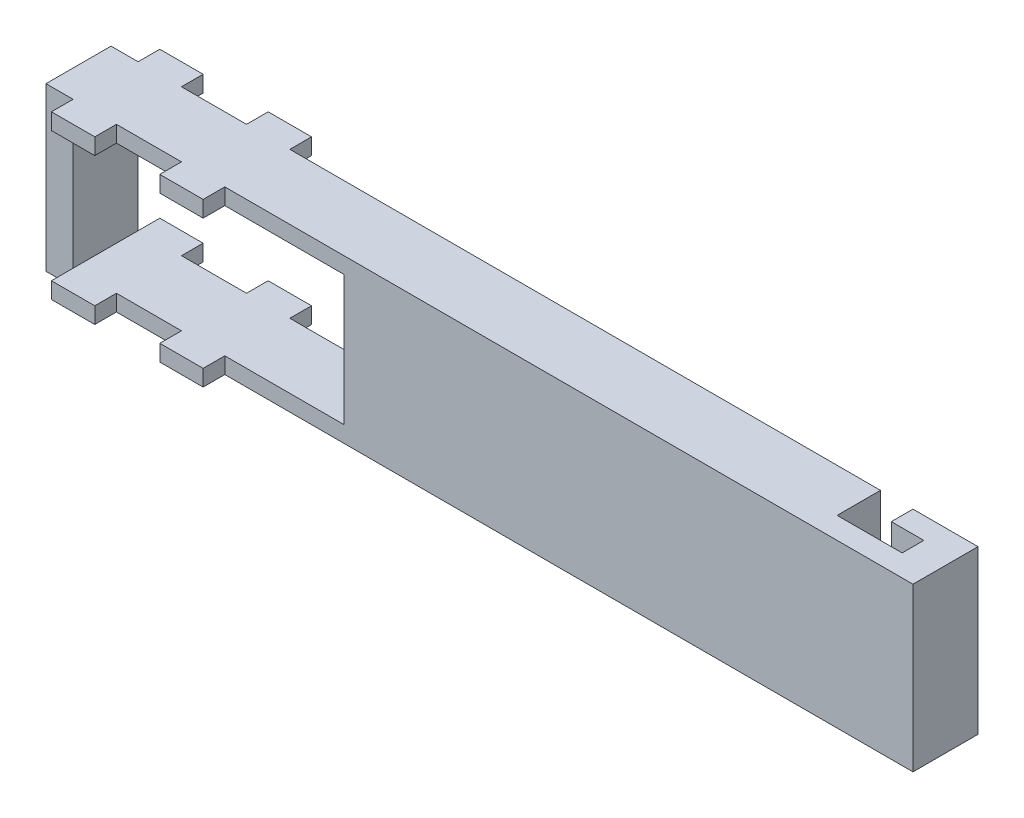
SolidWorks part; units mm, degrees
ref_plane "Front Plane" through (0, 0, 0) normal (0, 0, 1) x (1, 0, 0)
ref_plane "Top Plane" through (0, 0, 0) normal (0, 1, 0) x (1, 0, 0)
ref_plane "Right Plane" through (0, 0, 0) normal (1, 0, 0) x (0, 0, -1)
sketch "Sketch1" plane through (0, 0, 0) normal (0, 0, 1) x (1, 0, 0)
  line L1 (0, 0) -> (80, 0)
  line L2 (0, 0) -> (0, 15)
  line L3 (0, 15) -> (80, 15)
  line L4 (80, 0) -> (80, 15)
  dimension "D1" = 80
  dimension "D2" = 15
extrude "Boss-Extrude1" add sketch "Sketch1" along normal blind 6 contours L3 L4 L1 L2
sketch "Sketch2" plane through (0, 15, 0) normal (0, 1, 0) x (1, 0, 0)
  line L0 (74, 0) -> (74, -2)
  line L1 (0, 0) -> (80, 0) construction
  line L2 (74, -2) -> (77, -2)
  line L3 (77, -2) -> (77, -4)
  line L4 (77, -4) -> (71, -4)
  line L5 (71, -4) -> (71, 0)
  line L6 (71, 0) -> (74, 0)
  line L7 (80, -6) -> (80, 0) construction
  dimension "D1" = 9
  dimension "D2" = 2
  dimension "D3" = 2
  dimension "D4" = 6
  dimension "D5" = 3
extrude "Cut-Extrude1" cut sketch "Sketch2" against normal through all
sketch "Sketch3" plane through (0, 0, 6) normal (0, 0, 1) x (1, 0, 0)
  line L0 (0, 0) -> (0, 15) construction
  line L1 (2.5, 13.5) -> (27.5, 13.5)
  line L2 (2.5, 13.5) -> (2.5, 1.5)
  line L3 (2.5, 1.5) -> (27.5, 1.5)
  line L4 (27.5, 13.5) -> (27.5, 1.5)
  line L5 (0, 15) -> (80, 15) construction
  dimension "D1" = 12
  dimension "D2" = 2.5
  dimension "D3" = 1.5
  dimension "D4" = 25
extrude "Cut-Extrude2" cut sketch "Sketch3" against normal through all
sketch "Sketch4" plane through (0, 0, 6) normal (0, 0, 1) x (1, 0, 0)
  line L0 (0, 15) -> (80, 15) construction
  line L1 (2.5, 13.5) -> (6.5, 13.5)
  line L2 (2.5, 13.5) -> (2.5, 15)
  line L3 (2.5, 15) -> (6.5, 15)
  line L4 (6.5, 13.5) -> (6.5, 15)
  dimension "D1" = 4
extrude "Boss-Extrude2" add sketch "Sketch4" along normal blind 2
sketch "Sketch5" plane through (0, 0, 6) normal (0, 0, 1) x (1, 0, 0)
  line L0 (27.5, 13.5) -> (6.5, 13.5) construction
  line L1 (12.5, 13.5) -> (16.5, 13.5)
  line L2 (12.5, 13.5) -> (12.5, 15)
  line L3 (12.5, 15) -> (16.5, 15)
  line L4 (16.5, 13.5) -> (16.5, 15)
  line L5 (6.5, 15) -> (80, 15) construction
  line L6 (6.5, 13.5) -> (6.5, 15) construction
  dimension "D1" = 4
  dimension "D2" = 6
extrude "Boss-Extrude3" add sketch "Sketch5" along normal blind 2
sketch "Sketch6" plane through (0, 0, 6) normal (0, 0, 1) x (1, 0, 0)
  line L0 (0, 0) -> (80, 0) construction
  line L1 (2.5, 1.5) -> (6.5, 1.5)
  line L2 (2.5, 1.5) -> (2.5, 0)
  line L3 (2.5, 0) -> (6.5, 0)
  line L4 (6.5, 1.5) -> (6.5, 0)
  dimension "D1" = 4
sketch "Sketch7" plane through (0, 0, 6) normal (0, 0, 1) x (1, 0, 0)
  line L0 (2.5, 1.5) -> (27.5, 1.5) construction
  line L1 (12.5, 1.5) -> (16.5, 1.5)
  line L2 (12.5, 1.5) -> (12.5, 0)
  line L3 (12.5, 0) -> (16.5, 0)
  line L4 (16.5, 1.5) -> (16.5, 0)
  line L5 (0, 0) -> (80, 0) construction
  line L6 (12.5, 15) -> (12.5, 13.5) construction
  dimension "D1" = 0
  dimension "D2" = 4
extrude "Boss-Extrude4" add sketch "Sketch6" along normal blind 2 contours L4 L3 L2 L1
extrude "Boss-Extrude5" add sketch "Sketch7" along normal blind 2 contours L4 L3 L2 L1
sketch "Sketch9" plane through (0, 0, 0) normal (0, 0, -1) x (-1, 0, 0)
  line L0 (0, 15) -> (-71, 15) construction
  line L1 (-2.5, 13.5) -> (-6.5, 13.5)
  line L2 (-2.5, 13.5) -> (-2.5, 15)
  line L3 (-2.5, 15) -> (-6.5, 15)
  line L4 (-6.5, 13.5) -> (-6.5, 15)
  line L5 (-2.5, 13.5) -> (-2.5, 1.5) construction
  line L6 (-27.5, 13.5) -> (-2.5, 13.5) construction
  dimension "D1" = 4
  dimension "D2" = 0
  dimension "D3" = 0
extrude "Boss-Extrude6" add sketch "Sketch9" along normal blind 2
sketch "Sketch10" plane through (0, 0, 0) normal (0, 0, -1) x (-1, 0, 0)
  line L0 (-27.5, 13.5) -> (-6.5, 13.5) construction
  line L1 (-16.5, 13.5) -> (-12.5, 13.5)
  line L2 (-16.5, 13.5) -> (-16.5, 15)
  line L3 (-16.5, 15) -> (-12.5, 15)
  line L4 (-12.5, 13.5) -> (-12.5, 15)
  line L5 (-6.5, 15) -> (-71, 15) construction
  line L6 (-6.5, 15) -> (-6.5, 13.5) construction
  dimension "D1" = 6
  dimension "D2" = 4
extrude "Boss-Extrude7" add sketch "Sketch10" along normal blind 2
sketch "Sketch12" plane through (0, 0, 0) normal (0, 0, -1) x (-1, 0, 0)
  line L0 (0, 0) -> (-71, 0) construction
  line L1 (-2.5, 1.5) -> (-6.5, 1.5)
  line L2 (-2.5, 1.5) -> (-2.5, 0)
  line L3 (-2.5, 0) -> (-6.5, 0)
  line L4 (-6.5, 1.5) -> (-6.5, 0)
  line L5 (-2.5, 1.5) -> (-27.5, 1.5) construction
  line L6 (-16.5, 1.5) -> (-12.5, 1.5)
  line L7 (-16.5, 1.5) -> (-16.5, 0)
  line L8 (-16.5, 0) -> (-12.5, 0)
  line L9 (-12.5, 1.5) -> (-12.5, 0)
  line L10 (-16.5, 15) -> (-16.5, 13.5) construction
  dimension "D1" = 4
  dimension "D2" = 4
  dimension "D3" = 0
extrude "Boss-Extrude8" add sketch "Sketch12" along normal blind 2 contours L7 L8 L9 L6
extrude "Boss-Extrude9" add sketch "Sketch12<3>" along normal blind 2
sketch "Sketch12<3>" plane through (0, 0, 0) normal (0, 0, -1) x (-1, 0, 0) same geometry as "Sketch12"
